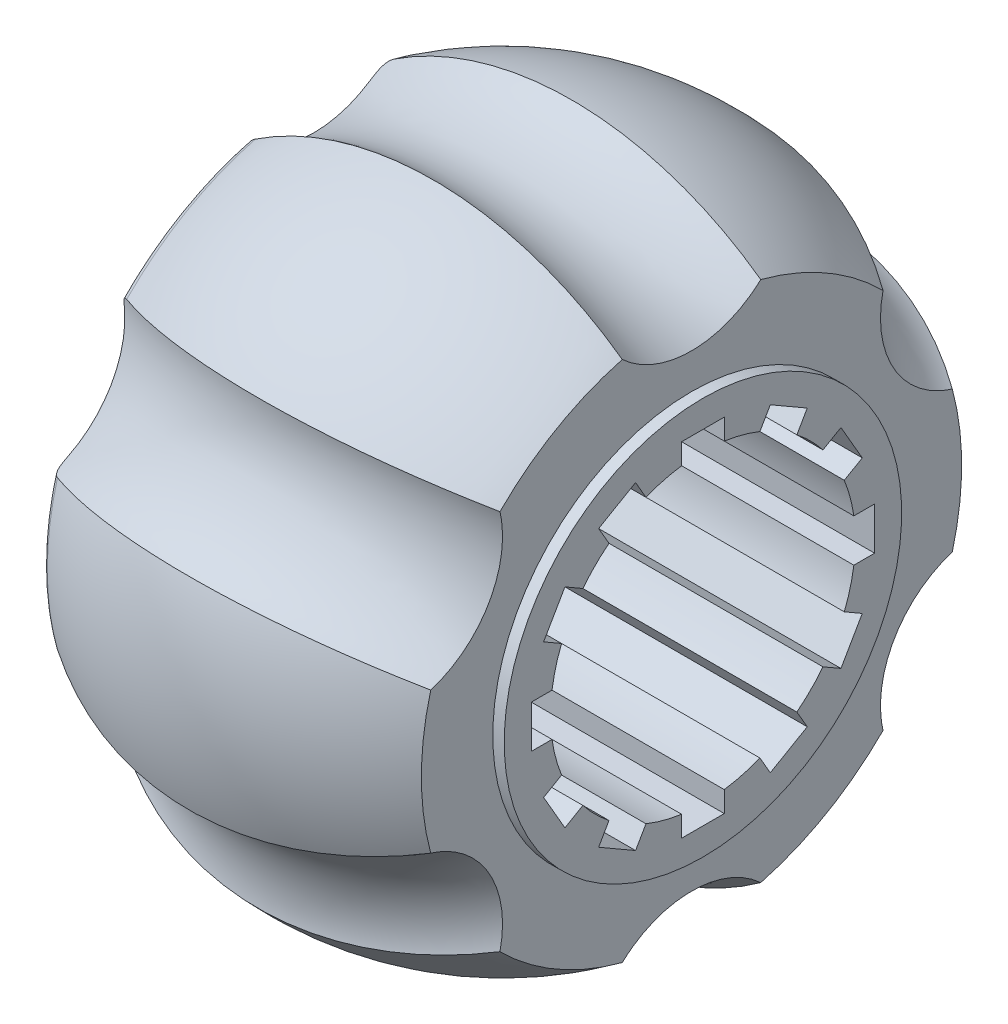
SolidWorks part; units mm, degrees
ref_plane "Front Plane" through (0, 0, 0) normal (0, 0, 1) x (1, 0, 0)
ref_plane "Top Plane" through (0, 0, 0) normal (0, 1, 0) x (1, 0, 0)
ref_plane "Right Plane" through (0, 0, 0) normal (1, 0, 0) x (0, 0, -1)
sketch "Sketch1" plane through (0, 0, 0) normal (0, 0, 1) x (1, 0, 0)
  line L0 (-33.4661, 0) -> (44.435, 0) construction
  line L1 (-17.2843, -26.6874) -> (144.7157, -26.6874) construction
  line L2 (13.3862, -4.8177) -> (13.3862, -10.6755)
  line L3 (159.0393, -26.9755) -> (-17.4489, -26.9755) construction
  line L4 (13.4271, -26.9755) -> (-22.4655, -26.9755)
  line L5 (13.3862, -10.6755) -> (14.324, -10.6755)
  line L6 (14.324, -10.6755) -> (14.324, -14.4755)
  line L7 (-17.6138, -13.4755) -> (-17.6138, -4.8367)
  line L8 (-16.6138, -14.4755) -> (13.4271, -14.4755)
  line L9 (14.324, -14.4755) -> (13.4271, -14.4755)
  line L10 (-16.6138, -14.4755) -> (-17.6138, -13.4755)
  arc A0 (-17.6138, -4.8367) -> (13.3862, -4.8177) centre (-2.1002, -26.9755) cw
  arc A1 (-17.6138, -0.8535) -> (13.3862, -0.8373) centre (-2.1002, -26.9755) cw
  point P13 (-17.6138, -14.4755)
  dimension "D3" = 3.8
  dimension "D4" = 31
  dimension "D1" = 25
  dimension "D2" = 162
revolve "Revolve1" add sketch "Sketch1" angle 360 about L4 region at (-1.9511, -7.9452, 0)
fillet "Fillet1" radius 2 1 edges at (-17.6138, -4.8367, 0)
ref_axis "Axis1" through (-16.6138, -26.9755, 0) along (1, 0, 0)
sketch "Sketch3" plane through (-17.6138, 0, 0) normal (-1, 0, 0) x (0, 0, 1)
  circle A0 centre (0, 0.5245) radius 8.335
  point P1 (0, 0.5245)
  dimension "D2" = 16.67
  dimension "D1" = 27.5
sketch "Sketch4" plane through (0, 0, 0) normal (0, 0, 1) x (1, 0, 0)
  arc A0 (-17.6138, -0.8535) -> (20.5011, -6.6724) centre (-2.1002, -26.9755) cw
  arc A1 (13.3862, -0.8373) -> (-17.6138, -0.8535) centre (-2.1002, -26.9755) ccw construction
sweep "Cut-Sweep2" cut profiles "Sketch3" path "Sketch4"
pattern_circular "CirPattern1" count 6 over 360 about axis through (-17.6138, -26.9755, 0) along (1, 0, 0) of "Cut-Sweep2"
sketch "Sketch5" plane through (-17.6138, 0, 0) normal (-1, 0, 0) x (0, 0, 1)
  line L1 (-14.08, -28.7255) -> (-11.0212, -28.7255)
  line L2 (-14.08, -28.7255) -> (-14.08, -25.2255)
  line L3 (-14.08, -25.2255) -> (-11.0212, -25.2255)
  line L4 (-11.0212, -28.7255) -> (-11.0212, -25.2255)
  point P0 (0, -26.9755)
  point P5 (-14.08, -26.9755)
  dimension "D1" = 3.5
extrude "Cut-Extrude1" cut sketch "Sketch5" against normal up to next
pattern_circular "CirPattern2" count 12 over 360 about axis through (-17.6138, -26.9755, 0) along (1, 0, 0) of "Cut-Extrude1"
curve "Curve1"
curve "Curve2"
